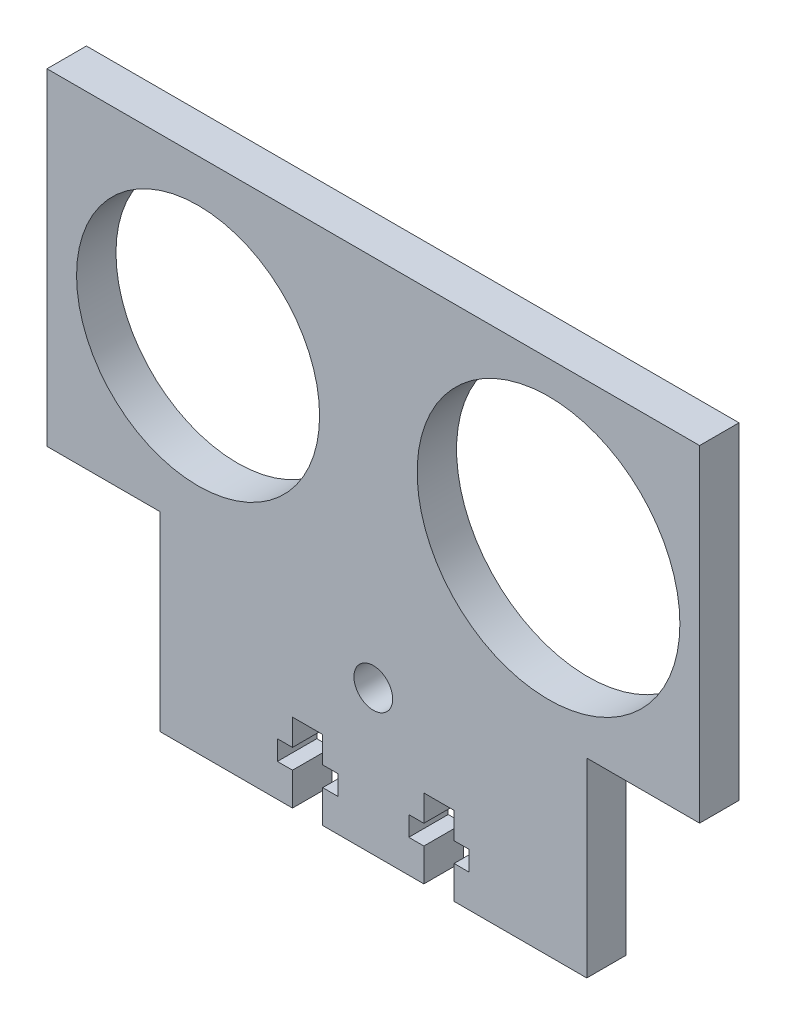
SolidWorks part; units mm, degrees
material "ABS"
ref_plane "Front Plane" through (0, 0, 0) normal (0, 0, 1) x (1, 0, 0)
ref_plane "Top Plane" through (0, 0, 0) normal (0, 1, 0) x (1, 0, 0)
ref_plane "Right Plane" through (0, 0, 0) normal (1, 0, 0) x (0, 0, -1)
sketch "Sketch1" plane through (0, 0, 0) normal (0, 0, 1) x (1, 0, 0)
  line L0 (0, 0) -> (-26.6757, 31.7908) construction
  line L1 (0, 0) -> (0, 56.7908) construction
  line L2 (-32.5, 7) -> (-32.5, -22)
  line L3 (-32.5, -22) -> (32.5, -22)
  line L4 (32.5, -22) -> (32.5, 7)
  line L5 (0, 0) -> (0, -22) construction
  line L6 (0, 0) -> (26.6757, 31.7908) construction
  line L10 (-32.5, 7) -> (-49.6757, 7)
  line L11 (-49.6757, 7) -> (-49.6757, 56.7908)
  line L12 (-49.6757, 56.7908) -> (49.6757, 56.7908)
  line L13 (49.6757, 56.7908) -> (49.6757, 7)
  line L14 (49.6757, 7) -> (32.5, 7)
  circle A0 centre (0, 0) radius 2.95
  circle A1 centre (26.6757, 31.7908) radius 20
  circle A2 centre (-26.6757, 31.7908) radius 18.5
  dimension "D1" = 5.9
  dimension "D9" = 37
  dimension "D11" = 40
  dimension "D2" = 41.5
  dimension "D4" = 40
  dimension "D5" = 22
  dimension "D6" = 65
  dimension "D3" = 23
  dimension "D7" = 25
  dimension "D8" = 29
  dimension "D10" = 40
extrude "Boss-Extrude1" add sketch "Sketch1" along normal blind 6
sketch "Sketch3" plane through (0, 0, 6) normal (0, 0, 1) x (1, 0, 0)
  line L0 (-32.5, -22) -> (32.5, -22) construction
  line L1 (-12.3, -22) -> (-7.7, -22)
  line L2 (-12.3, -22) -> (-12.3, -17)
  line L3 (-12.3, -10) -> (-7.7, -10)
  line L4 (-7.7, -22) -> (-7.7, -17)
  line L5 (0, 0) -> (0, -22) construction
  line L6 (-7.7, -14) -> (-5.4, -14)
  line L7 (-14.6, -14) -> (-12.3, -14)
  line L8 (-14.6, -14) -> (-14.6, -17)
  line L9 (-14.6, -17) -> (-12.3, -17)
  line L10 (-5.4, -14) -> (-5.4, -17)
  line L11 (-12.3, -14) -> (-12.3, -10)
  line L12 (-7.7, -17) -> (-5.4, -17)
  line L13 (-7.7, -14) -> (-7.7, -10)
  line L14 (7.7, -14) -> (7.7, -10)
  line L15 (7.7, -17) -> (5.4, -17)
  line L16 (12.3, -14) -> (12.3, -10)
  line L17 (5.4, -14) -> (5.4, -17)
  line L18 (14.6, -17) -> (12.3, -17)
  line L19 (14.6, -14) -> (14.6, -17)
  line L20 (14.6, -14) -> (12.3, -14)
  line L21 (7.7, -14) -> (5.4, -14)
  line L22 (7.7, -22) -> (7.7, -17)
  line L23 (12.3, -10) -> (7.7, -10)
  line L24 (12.3, -22) -> (12.3, -17)
  line L25 (12.3, -22) -> (7.7, -22)
  point P6 (-10, -10)
  point P18 (-13.45, -17)
  dimension "D1" = 4.6
  dimension "D2" = 10
  dimension "D3" = 12
  dimension "D4" = 9.2
  dimension "D5" = 3
  dimension "D6" = 5
extrude "Cut-Extrude2" cut sketch "Sketch3" against normal through all
equation "\"smallPulleyTeeth\"= 15"
equation "\"largePulleyTeeth\"= 30"
equation "\"eighthThick\"= 2.9mm"
equation "\"sixteenthThick\" = 1.7mm"
equation "\"quarterThick\"=6.0mm"
equation "\"OD\" = 145mm"
equation "\"puckAngle\" = 60.5deg"
equation "\"puckDiam\" = 76.5mm"
equation "\"axlePress\" = 5.9mm"
equation "\"D1@Sketch1\"=\"axlePress\""
equation "\"D1@Boss-Extrude1\"=\"quarterThick\""
equation "\"press\" = 0.2mm"
equation "\"wheelClear\" = 0.3mm"
equation "\"10-32clear\" = 4.8mm"
equation "\"D1@Sketch3\"=\"10-32clear\"-\"press\""
equation "\"6-32clear\" = 3.3mm"
equation "\"8-32clear\" = 4.0mm"
equation "\"wheelHeight\" = 22mm"
equation "\"D5@Sketch1\"=\"wheelHeight\""
equation "\"D8@Sketch1\"=\"eighthThick\"*10"
equation "\"4-40clear\" = 3.0mm"
equation "\"wheelWell\" = 65mm"
equation "\"D6@Sketch1\"=\"wheelWell\""
